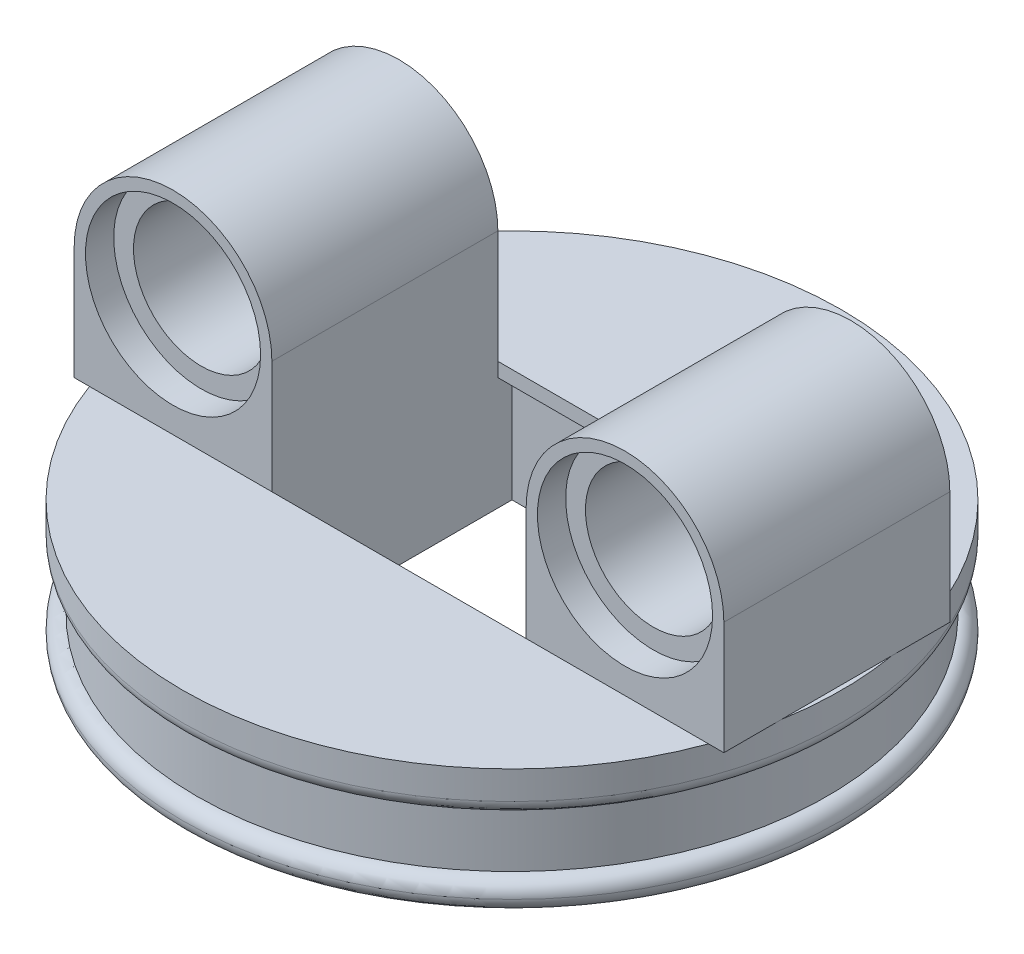
SolidWorks part; units mm, degrees
ref_plane "Front Plane" through (0, 0, 0) normal (0, 0, 1) x (1, 0, 0)
ref_plane "Top Plane" through (0, 0, 0) normal (0, 1, 0) x (1, 0, 0)
ref_plane "Right Plane" through (0, 0, 0) normal (1, 0, 0) x (0, 0, -1)
sketch "Sketch6" plane through (0, 0, 0) normal (0, 0, 1) x (1, 0, 0)
  line L1 (-11.5, 4) -> (-11.5, 0)
  line L3 (-4.5, 4) -> (-4.5, 0)
  line L4 (4.5, 4) -> (4.5, 0)
  line L5 (11.5, 4) -> (11.5, 0)
  line L6 (-11.5, 0) -> (-4.5, 0)
  line L7 (4.5, 0) -> (11.5, 0)
  arc A4 (-11.5, 4) -> (-4.5, 4) centre (-8, 4) cw
  arc A5 (4.5, 4) -> (11.5, 4) centre (8, 4) cw
extrude "Boss-Extrude1" add sketch "Sketch6" along normal mid plane 8
sketch "Sketch7" plane through (0, 0, 4) normal (0, 0, 1) x (1, 0, 0)
  circle A2 centre (-8, 4) radius 2.4
  dimension "D3" = 4.8
extrude "Cut-Extrude1" cut sketch "Sketch7" against normal blind 8 contours A2
sketch "Sketch8" plane through (0, 0, 4) normal (0, 0, 1) x (1, 0, 0)
  circle A0 centre (-8, 4) radius 3.1
  dimension "D1" = 6.2
extrude "Cut-Extrude2" cut sketch "Sketch8" against normal blind 1
mirror "Mirror1" about plane through (0, 0, 0) normal (0, 0, 1) of "Cut-Extrude2"
sketch "Sketch9" plane through (0, 0, 4) normal (0, 0, 1) x (1, 0, 0)
  circle A2 centre (8, 4) radius 2.4
  dimension "D2" = 4.8
extrude "Cut-Extrude3" cut sketch "Sketch9" against normal blind 8
sketch "Sketch10" plane through (0, 0, 4) normal (0, 0, 1) x (1, 0, 0)
  circle A0 centre (8, 4) radius 3.1
  dimension "D1" = 6.2
extrude "Cut-Extrude4" cut sketch "Sketch10" against normal blind 1
mirror "Mirror3" about plane through (0, 0, 0) normal (0, 0, 1) of "Cut-Extrude4"
sketch "Sketch11" plane through (0, 0, 0) normal (0, 1, 0) x (1, 0, 0)
  circle A0 centre (0, 0) radius 11.665
  dimension "D1" = 23.33
extrude "Boss-Extrude2" add sketch "Sketch11" against normal blind 0.5
sketch "Sketch13" plane through (0, -0.5, 0) normal (0, -1, 0) x (1, 0, 0)
  circle A2 centre (0, 0) radius 10.665
  circle A3 centre (0, 0) radius 11.665
extrude "Boss-Extrude3" add sketch "Sketch13" along normal blind 1
sketch "Sketch14" plane through (0, -1.5, 0) normal (0, -1, 0) x (1, 0, 0)
  circle A0 centre (0, 0) radius 10.665
  circle A1 centre (0, 0) radius 11.165
extrude "Boss-Extrude4" add sketch "Sketch14" along normal blind 2
sketch "Sketch15" plane through (0, -3.5, 0) normal (0, -1, 0) x (1, 0, 0)
  circle A0 centre (0, 0) radius 11.665
  circle A1 centre (0, 0) radius 10.665
  dimension "D1" = 23.33
extrude "Boss-Extrude5" add sketch "Sketch15" along normal blind 1
fillet "Fillet1" radius 0.5 1 edges at (0, -3.5, -11.665)
fillet "Fillet2" radius 0.5 1 edges at (0, -4.5, -11.665)
fillet "Fillet3" radius 0.5 1 edges at (0, -1.5, -11.665)
sketch "Sketch16" plane through (0, 0, 0) normal (0, 1, 0) x (1, 0, 0)
  line L0 (4.5, 4) -> (4.5, -4)
  line L1 (4.5, -4) -> (-4.5, -4)
  line L2 (-4.5, -4) -> (-4.5, 4)
  line L3 (-4.5, 4) -> (4.5, 4)
extrude "Cut-Extrude5" cut sketch "Sketch16" against normal blind 0.5
ref_plane "Plane1" through (4.5, -0.5, 4) normal (1, 0, 0) x (0, 0, -1)
sketch "Sketch18" plane through (0, -0.5, 0) normal (0, -1, 0) x (1, 0, 0)
  line L0 (-4.5, -4.5) -> (-4.5, 4.5)
  line L2 (-4.5, 4.5) -> (4.5, 4.5)
  line L3 (4.5, 1.525) -> (4.5, 6.475) construction
  line L4 (-4.5, -4.5) -> (4.5, -4.5)
  line L5 (4.5, -4.5) -> (4.5, 4.5)
  line L15 (-5, 5) -> (-5, -5)
  line L16 (-5, -5) -> (5, -5)
  line L17 (5, -5) -> (5, 5)
  line L18 (5, 5) -> (-5, 5)
  point P3 (-4.5, 0)
  dimension "D1" = 9
extrude "Boss-Extrude6" add sketch "Sketch18" along normal blind 4
